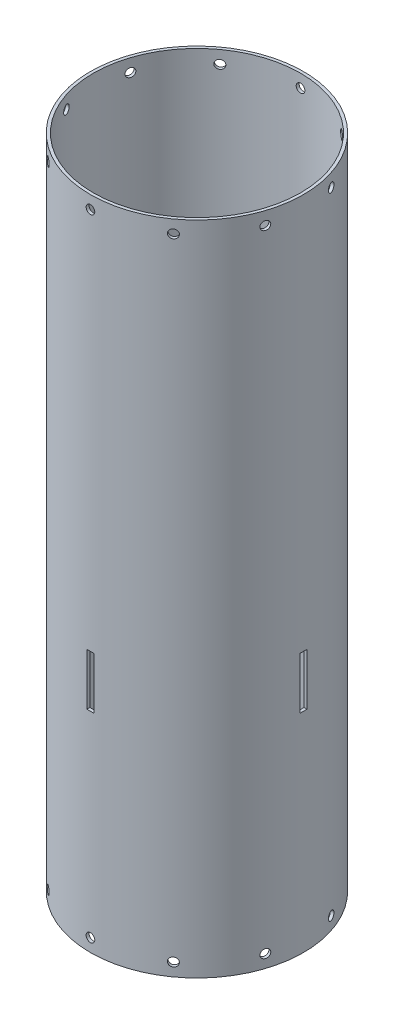
SolidWorks part; units mm, degrees
material "Acrylic (Medium-high impact)"
ref_plane "Front Plane" through (0, 0, 0) normal (0, 0, 1) x (1, 0, 0)
ref_plane "Top Plane" through (0, 0, 0) normal (0, 1, 0) x (1, 0, 0)
ref_plane "Right Plane" through (0, 0, 0) normal (1, 0, 0) x (0, 0, -1)
sketch "Sketch1" plane through (0, 0, 0) normal (0, 1, 0) x (1, 0, 0)
  circle A0 centre (0, 0) radius 76.2
  circle A1 centre (0, 0) radius 78.359
  dimension "D1" = 152.4
  dimension "D2" = 156.718
extrude "Boss-Extrude1" add sketch "Sketch1" along normal blind 482.6
sketch "Sketch2" plane through (0, 0, 0) normal (0, 0, 1) x (1, 0, 0)
  line L0 (0, 0) -> (0, 105.6712) construction
  line L1 (-76.2, 0) -> (76.2, 0) construction
  line L2 (-78.359, 0) -> (78.359, 0) construction
  line L3 (78.359, 241.3) -> (42.8908, 241.3) construction
  line L4 (78.359, 0) -> (78.359, 482.6) construction
  circle A0 centre (0, 9.525) radius 3.175
  circle A1 centre (0, 473.075) radius 3.175
  dimension "D1" = 6.35
  dimension "D2" = 9.525
extrude "Cut-Extrude1" cut sketch "Sketch2" against normal through all
ref_axis "Axis1" through (0, 0, 0) along (0, 1, 0)
pattern_circular "CirPattern1" count 10 over 360 about axis through (0, 0, 0) along (0, 1, 0) of "Cut-Extrude1" reverse direction yes
sketch "Sketch3" plane through (0, 0, 0) normal (0, 0, 1) x (1, 0, 0)
  line L0 (0, 0) -> (0, 105.6712) construction
  line L1 (-2.54, 153.67) -> (2.54, 153.67)
  line L2 (-2.54, 153.67) -> (-2.54, 191.77)
  line L3 (-2.54, 191.77) -> (2.54, 191.77)
  line L4 (2.54, 153.67) -> (2.54, 191.77)
  line L5 (-2.54, 153.67) -> (2.54, 191.77) construction
  line L6 (-2.54, 191.77) -> (2.54, 153.67) construction
  line L7 (-76.2, 0) -> (76.2, 0) construction
  line L8 (0, 482.6) -> (0, 408.1695) construction
  line L9 (76.2, 482.6) -> (-76.2, 482.6) construction
  point P0 (0, 172.72)
  dimension "D1" = 153.67
  dimension "D2" = 38.1
  dimension "D3" = 5.08
extrude "Cut-Extrude2" cut sketch "Sketch3" against normal through all
ref_axis "Axis2" through (0, 482.6, 0) along (0, -1, 0)
pattern_circular "CirPattern2" count 4 over 360 about axis through (0, 482.6, 0) along (0, -1, 0) of "Cut-Extrude2"
